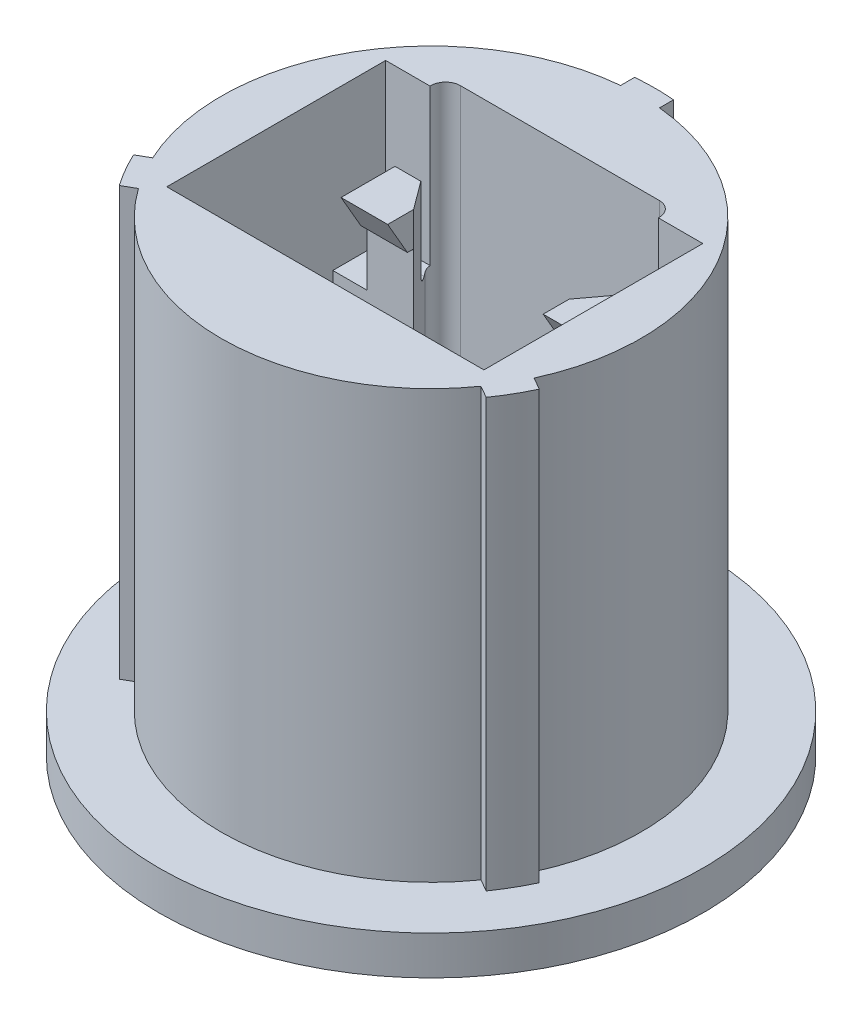
SolidWorks part; units mm, degrees
ref_plane "Front Plane" through (0, 0, 0) normal (0, 0, 1) x (1, 0, 0)
ref_plane "Top Plane" through (0, 0, 0) normal (0, 1, 0) x (1, 0, 0)
ref_plane "Right Plane" through (0, 0, 0) normal (1, 0, 0) x (0, 0, -1)
sketch "Sketch1" plane through (0, 0, 0) normal (0, 1, 0) x (1, 0, 0)
  line L0 (-0.7938, 9.1095) -> (-0.7938, 8.5357)
  line L1 (0.7937, 9.1095) -> (0.7937, 8.5357)
  line L2 (8.2859, -3.8673) -> (7.789, -3.5804)
  line L3 (7.4922, -5.2421) -> (6.9952, -4.9552)
  line L4 (-7.4922, -5.2421) -> (-6.9952, -4.9552)
  line L5 (-8.2859, -3.8673) -> (-7.789, -3.5804)
  arc A0 (-6.9952, -4.9552) -> (6.9952, -4.9552) centre (0, 0) ccw
  arc A1 (-8.2859, -3.8673) -> (-7.4922, -5.2421) centre (0, 0) ccw
  arc A2 (0.7937, 9.1095) -> (-0.7938, 9.1095) centre (0, 0) ccw
  arc A3 (7.4922, -5.2421) -> (8.2859, -3.8673) centre (0, 0) ccw
  arc A4 (7.789, -3.5804) -> (0.7937, 8.5357) centre (0, 0) ccw
  arc A5 (-0.7938, 8.5357) -> (-7.789, -3.5804) centre (0, 0) ccw
  point P18 (0, 0)
  dimension "D1" = 17.145
  dimension "D2" = 18.288
  dimension "D3" = 1.5875
  dimension "D4" = 3
extrude "Boss-Extrude1" add sketch "Sketch1" along normal blind 19.05
sketch "Sketch2" plane through (0, 19.05, 0) normal (0, 1, 0) x (1, 0, 0)
  line L0 (-3.175, 2.4638) -> (-4.5436, 4.3031)
  line L1 (-6.477, 2.4638) -> (6.477, 2.4638)
  line L2 (-6.477, 2.4638) -> (-6.477, 0.762)
  line L3 (-6.477, 0.762) -> (6.477, 0.762)
  line L4 (6.477, 2.4638) -> (6.477, 0.762)
  line L5 (-4.064, 5.2578) -> (4.064, 5.2578)
  line L6 (4.5436, 4.3031) -> (3.175, 2.4638)
  line L7 (3.175, 2.4638) -> (-3.175, 2.4638)
  arc A0 (-4.5436, 4.3031) -> (-4.064, 5.2578) centre (-4.064, 4.66) cw
  arc A1 (4.064, 5.2578) -> (4.5436, 4.3031) centre (4.064, 4.66) cw
  point P12 (0, 5.2578)
  point P13 (0, 2.4638)
  dimension "D1" = 1.7018
  dimension "D2" = 12.954
  dimension "D3" = 8.128
  dimension "D4" = 6.35
  dimension "D5" = 2.794
  dimension "D6" = 0.762
extrude "Cut-Extrude1" cut sketch "Sketch2" against normal through all contours A1 L5 A0 L0 L1 L6 region at (0, 19.05, -3.9469)
extrude "Cut-Extrude2" cut sketch "Sketch2<4>" against normal blind 18.2562 contours L4 L1 L2 L3 region at (0, 19.05, -1.6129)
sketch "Sketch2<4>" plane through (0, 19.05, 0) normal (0, 1, 0) x (1, 0, 0) same geometry as "Sketch2"
sketch "Sketch6" plane through (0, 0, 0) normal (1, 0, 0) x (0, 0, -1)
  line L0 (8.5357, 1.5875) -> (9.144, 1.5875)
  line L1 (8.5357, 1.5875) -> (8.5357, 0)
  line L3 (8.5357, 0) -> (9.144, 0)
  line L5 (9.144, 0) -> (9.144, 1.5875)
  line L6 (0, 19.7302) -> (0, -0.9338) construction
  dimension "D1" = 1.5875
revolve "Cut-Revolve2" cut sketch "Sketch6" angle 360 about L6
sketch "Sketch8" plane through (0, 0, 0) normal (1, 0, 0) x (0, 0, -1)
  line L1 (8.5357, 1.5875) -> (11.1125, 1.5875)
  line L2 (8.5357, 1.5875) -> (8.5357, 0)
  line L3 (8.5357, 0) -> (11.1125, 0)
  line L4 (11.1125, 1.5875) -> (11.1125, 0)
  line L8 (0, 4.4839) -> (0, -1.895) construction
  dimension "D1" = 11.1125
revolve "Revolve2" add sketch "Sketch8" angle 360 about L8
sketch "Sketch9" plane through (0, 19.05, 0) normal (0, 1, 0) x (1, 0, 0)
  line L1 (-6.477, 0.762) -> (6.477, 0.762)
  line L2 (-6.477, 0.762) -> (-6.477, -4.318)
  line L3 (-6.477, -4.318) -> (6.477, -4.318)
  line L4 (6.477, 0.762) -> (6.477, -4.318)
  line L5 (-6.477, 2.4638) -> (6.477, 2.4638)
  line L6 (-6.477, 2.4638) -> (-6.477, 4.6228)
  line L7 (-6.477, 4.6228) -> (6.477, 4.6228)
  line L8 (6.477, 2.4638) -> (6.477, 4.6228)
  dimension "D1" = 5.08
  dimension "D2" = 2.159
extrude "Cut-Extrude3" cut sketch "Sketch9" against normal blind 6.35
sketch "Sketch10" plane through (0, 12.7, 0) normal (0, 1, 0) x (1, 0, 0)
  line L0 (-3.175, 2.4638) -> (-4.0255, 3.6068)
  line L1 (-6.477, 2.4638) -> (-3.175, 2.4638) construction
  line L2 (-3.175, 2.4638) -> (-4.5436, 4.3031) construction
  line L3 (-4.0255, 3.6068) -> (-5.08, 3.6068)
  line L4 (-5.08, 3.6068) -> (-5.08, 2.4638)
  line L5 (-5.08, 2.4638) -> (-3.175, 2.4638)
  dimension "D1" = 1.143
  dimension "D2" = 1.905
extrude "Boss-Extrude2" add sketch "Sketch10" along normal blind 2.54
sketch "Sketch11" plane through (0, 0, -2.4638) normal (0, 0, 1) x (1, 0, 0)
  line L0 (-5.08, 15.24) -> (-5.08, 15.113)
  line L1 (-5.08, 15.24) -> (-5.08, 12.7) construction
  line L2 (-5.08, 15.113) -> (-3.175, 15.113)
  line L3 (-3.175, 0.7938) -> (-3.175, 15.24) construction
  line L4 (-3.175, 15.113) -> (-3.175, 15.24)
  line L5 (-3.175, 15.24) -> (-5.08, 15.24)
  dimension "D1" = 0.127
extrude "Boss-Extrude3" add sketch "Sketch11" along normal blind 0.254
fillet "Fillet1" radius 0.508 1 edges at (-4.5528, 12.7, -3.6068)
fillet "Fillet2" radius 0.0635 1 edges at (-4.1275, 15.113, -2.4638)
sketch "Sketch12" plane through (0, 15.24, 0) normal (0, 1, 0) x (1, 0, 0)
  line L0 (-3.175, 2.2098) -> (-3.175, 2.4638)
  line L1 (-3.175, 2.4638) -> (-4.0255, 3.6068)
  line L2 (-4.0255, 3.6068) -> (-5.08, 3.6068)
  line L3 (-5.08, 3.6068) -> (-5.08, 2.2098)
  line L4 (-5.08, 2.2098) -> (-3.175, 2.2098)
extrude "Boss-Extrude4" add sketch "Sketch12" along normal blind 1.27
sketch "Sketch13" plane through (-3.175, 0, 0) normal (1, 0, 0) x (0, 0, -1)
  line L0 (2.2098, 15.113) -> (1.4032, 16.51)
  line L2 (2.2098, 16.51) -> (1.4032, 16.51)
  line L3 (2.2098, 15.113) -> (2.2098, 16.51)
  point P1 (0, 0)
  dimension "D1" = 30
extrude "Boss-Extrude5" add sketch "Sketch13" against normal blind 1.905
mirror "Mirror1" about plane through (0, 0, 0) normal (1, 0, 0) of "Boss-Extrude5", "Boss-Extrude4", "Fillet1", "Boss-Extrude3", "Boss-Extrude2"
